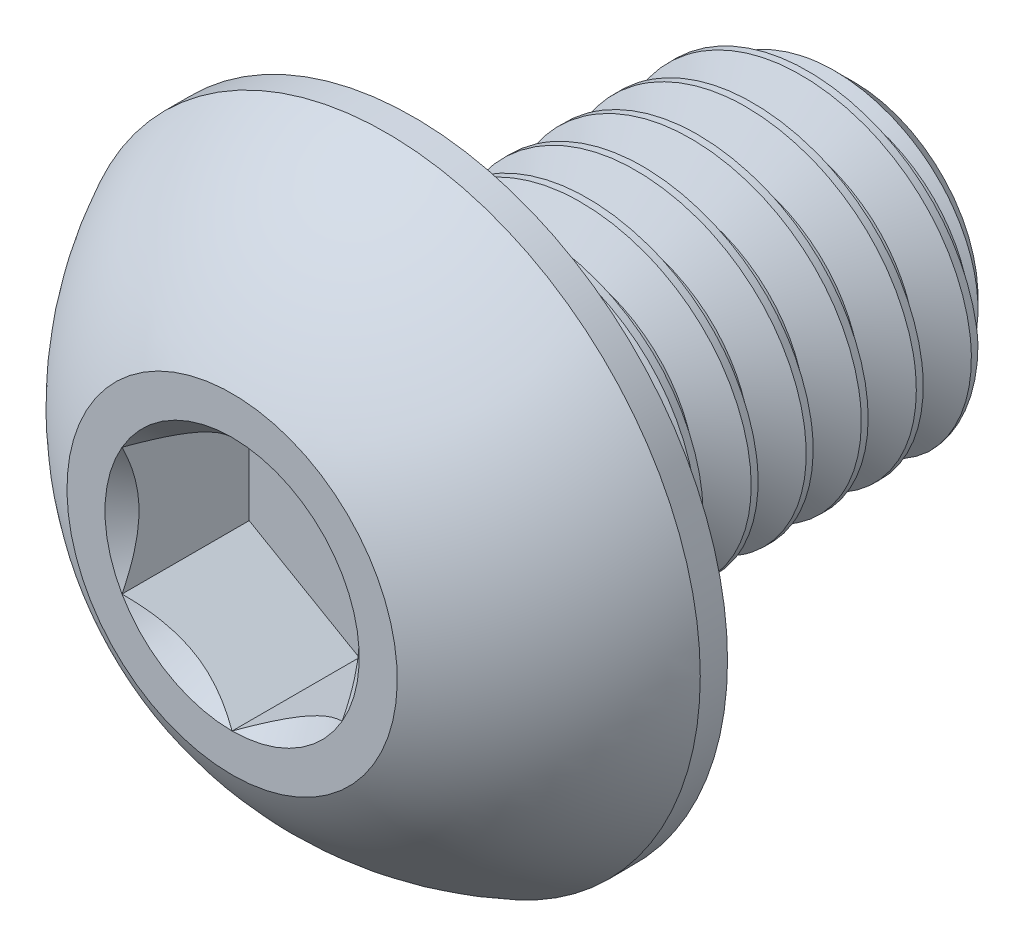
SolidWorks part; units mm, degrees
ref_plane "Front" through (0, 0, 0) normal (0, 0, 1) x (1, 0, 0)
ref_plane "Top" through (0, 0, 0) normal (0, 1, 0) x (1, 0, 0)
ref_plane "Right" through (0, 0, 0) normal (1, 0, 0) x (0, 0, -1)
sketch "Sketch1" plane through (0, 0, 0) normal (1, 0, 0) x (0, 0, -1)
  line L2 (1.65, 1.5) -> (5.65, 1.5)
  line L3 (5.65, 1.5) -> (5.65, 0)
  line L4 (5.65, 0) -> (1.65, 0)
  line L6 (1.4025, 2.85) -> (1.65, 2.85) construction
  line L7 (5.65, 1.5) -> (5.65, -1.5) construction
  line L8 (0, 0) -> (1.65, 0) construction
  line L9 (1.65, 2.85) -> (1.65, -2.85) construction
  line L11 (1.65, 1.5) -> (1.65, 0)
  line L13 (0, 1) -> (0, -1) construction
  line L14 (0, 1) -> (0, 1.5) construction
  arc A3 (0, 1.5) -> (1.4025, 2.85) centre (2.7948, 0) cw construction
  dimension "D1" = 0.2475
revolve "Revolve1" add sketch "Sketch1" angle 360 mid plane about L4
sketch "Sketch3" plane through (0, 0, -5.65) normal (0, 0, -1) x (-1, 0, 0)
  circle A0 centre (0, 0) radius 1.5
curve "Helix/Spiral1" pitch 0.5 height 4.5 radius 1.5 centre (0, 0, -5.65) axis (0, 0, 1) start towards (0, 1, 0)
sketch "Sketch2" plane through (0, 0, 0) normal (1, 0, 0) x (0, 0, -1)
  line L0 (5.65, 1.5) -> (6.0875, 1.5)
  line L1 (6.0875, 1.5) -> (5.9, 1.1752)
  line L2 (5.9, 1.1752) -> (5.8375, 1.1752)
  line L3 (5.8375, 1.1752) -> (5.65, 1.5)
  line L4 (5.7438, 1.3376) -> (5.9938, 1.3376) construction
  dimension "D1" = 60
  dimension "D2" = 0.0625
  dimension "D3" = 0.25
chamfer "Chamfer1" distance 0.375 angle 45 1 edges at (0, 1.5, -5.65)
sweep "Cut-Sweep1" cut profiles "Sketch2" path "Helix/Spiral1" align with end faces yes
sketch "Sketch7" plane through (0, 0, 0) normal (1, 0, 0) x (0, 0, -1)
  line L6 (1.4025, 2.85) -> (1.65, 2.85) construction
  line L8 (0, 0) -> (1.65, 0) construction
  line L11 (1.65, 2.85) -> (1.65, -2.85) construction
  line L12 (1.4025, 2.85) -> (1.65, 2.85)
  line L13 (0, 0) -> (1.65, 0)
  line L14 (0, 1) -> (0, -1) construction
  line L15 (1.65, 2.85) -> (1.65, 0)
  line L16 (0, 1.5) -> (0, 0)
  arc A2 (1.4025, 2.85) -> (0, 1.5) centre (2.7948, 0) ccw construction
  arc A3 (1.4025, 2.85) -> (0, 1.5) centre (2.7948, 0) ccw
revolve "Revolve2" add sketch "Sketch7" angle 360 mid plane about L13
sketch "Sketch5" plane through (0, 0, 0) normal (0, 0, 1) x (1, 0, 0)
  line L1 (1, -0.5774) -> (1, 0.5774)
  line L2 (1, 0.5774) -> (0, 1.1547)
  line L3 (0, 1.1547) -> (-1, 0.5774)
  line L4 (-1, 0.5774) -> (-1, -0.5774)
  line L5 (-1, -0.5774) -> (0, -1.1547)
  line L6 (0, -1.1547) -> (1, -0.5774)
  circle A0 centre (0, 0) radius 1 construction
extrude "Cut-Extrude2" cut sketch "Sketch5" against normal blind 1.155
sketch "Sketch6" plane through (0, 0, 0) normal (0, 0, 1) x (1, 0, 0)
  circle A0 centre (0, 0) radius 1.1547
extrude "Cut-Extrude3" cut sketch "Sketch6" against normal blind 1.155 draft 45
sketch "Sketch9" [suppressed] plane through (0, 0, -4.2164) normal (0, 0, 1) x (1, 0, 0)
  circle A2 centre (0, 0) radius 3.9687
extrude "Boss-Extrude2" [suppressed] add sketch "Sketch9" against normal offset from surface (9.525 mm away) 28.575 up to face at (0, 1.125, -5.65)
sketch "Sketch10" plane through (0, 0, 0) normal (1, 0, 0) x (0, 0, -1)
  line L0 (5.65, 1.5) -> (5.65, -1.5) construction
  point P0 (4.9, -1.5)
  dimension "D1" = 0.75
equation "\"D3@Helix/Spiral1\" = \"Lg@Sketch1\" + \"D4@Helix/Spiral1\""
equation "\"D2@Sketch2\" = \"D4@Helix/Spiral1\" * .125"
equation "\"D3@Sketch2\" = \"D4@Helix/Spiral1\" * .5"
equation "\"D1@Chamfer1\" = \"D4@Helix/Spiral1\" * .75"
equation "\"D1@Cut-Extrude2\" = \"Head Ht@Sketch1\" * .7"
equation "\"D1@Sketch1\" = \"Head Ht@Sketch1\" * .15"
equation "\"D1@Sketch10\" = \"D4@Helix/Spiral1\" * 1.5"
equation "\"D1@Cut-Extrude3\" = \"D1@Cut-Extrude2\""
